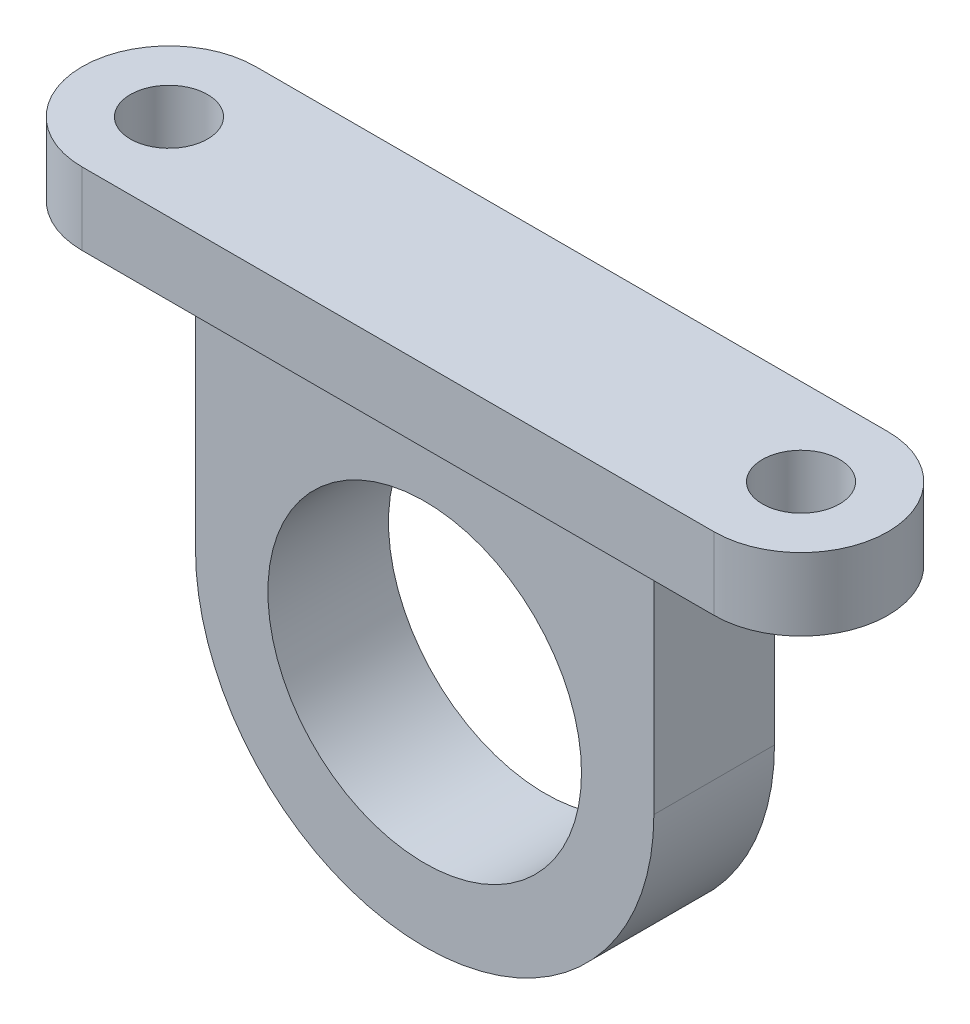
SolidWorks part; units mm, degrees
material "Plain Carbon Steel"
ref_plane "Front Plane" through (0, 0, 0) normal (0, 0, 1) x (1, 0, 0)
ref_plane "Top Plane" through (0, 0, 0) normal (0, 1, 0) x (1, 0, 0)
ref_plane "Right Plane" through (0, 0, 0) normal (1, 0, 0) x (0, 0, -1)
sketch "Sketch1" plane through (0, 0, 0) normal (0, 0, 1) x (1, 0, 0)
  line L0 (-9.5, 0) -> (-9.5, 9.5)
  line L1 (9.5, 0) -> (9.5, 9.5)
  line L2 (-9.5, 9.5) -> (9.5, 9.5)
  circle A0 centre (0, 0) radius 6.5
  arc A1 (-9.5, 0) -> (9.5, 0) centre (0, 0) ccw
  circle A2 centre (0, 0) radius 9.5 construction
  dimension "D1" = 13
  dimension "D3" = 9.5
  dimension "D2" = 3
extrude "Boss-Extrude1" add sketch "Sketch1" along normal blind 5
sketch "Sketch2" plane through (0, 9.5, 0) normal (0, 1, 0) x (1, 0, 0)
  line L4 (0, 1.1) -> (0, 0) construction
  line L5 (0, 0) -> (0, -5) construction
  line L15 (13.1, 1.1) -> (-13.1, 1.1)
  line L16 (9.5, -5) -> (-9.5, -5) construction
  line L22 (0, -5) -> (0, -6.1) construction
  line L23 (-9.5, -5) -> (-9.5, 0) construction
  line L31 (-13.1, -6.1) -> (13.1, -6.1)
  circle A0 centre (-13.1, -2.5) radius 1.6
  arc A1 (-13.1, 1.1) -> (-13.1, -6.1) centre (-13.1, -2.5) ccw
  arc A2 (13.1, 1.1) -> (13.1, -6.1) centre (13.1, -2.5) cw
  circle A3 centre (13.1, -2.5) radius 1.6
  line M3 (9.5, 0) -> (-9.5, 0)
  line M4 (-9.5, 0) -> (-9.5, -5)
  line M5 (-9.5, -5) -> (9.5, -5)
  line M6 (9.5, -5) -> (9.5, 0)
  dimension "D2" = 3.2
  dimension "D1" = 3.6
  dimension "D3" = 3.6
extrude "Boss-Extrude2" add sketch "Sketch2" along normal blind 3 contours M6 M3 M4 M5 | M4 | M6 region at (16.3583, 9.5, 2.5) region at (0, 9.5, 2.5)
